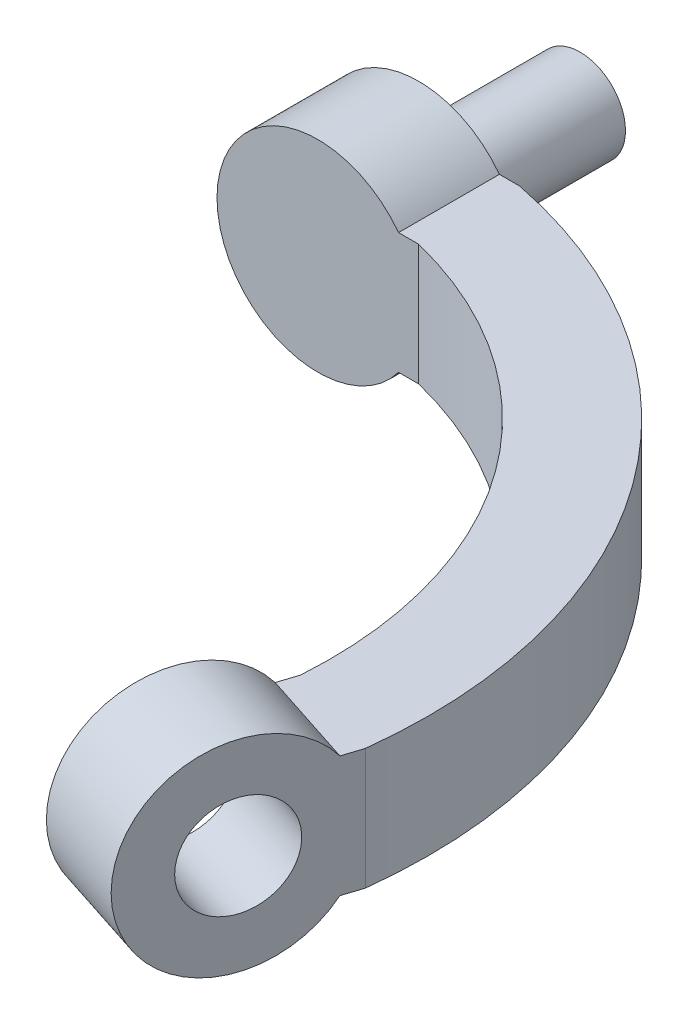
SolidWorks part; units mm, degrees
ref_plane "前视基准面" through (0, 0, 0) normal (0, 0, 1) x (1, 0, 0)
ref_plane "上视基准面" through (0, 0, 0) normal (0, 1, 0) x (1, 0, 0)
ref_plane "右视基准面" through (0, 0, 0) normal (1, 0, 0) x (0, 0, -1)
other "Configuration Table"
sketch "草图2" plane through (0, 0, 0) normal (0, 0, 1) x (1, 0, 0)
  circle A0 centre (0, 0) radius 5
  dimension "D1" = 10
extrude "凸台-拉伸3" add sketch "草图2" along normal blind 5
sketch "草图3" plane through (0, 0, 0) normal (0, 1, 0) x (1, 0, 0)
  line L0 (0, 0) -> (0, -25) construction
  line L1 (0, -25) -> (22.125, -32.1888) construction
  line L2 (20.5662, -26.4251) -> (25.3215, -27.9701)
  line L3 (0, 0) -> (5, 0)
  line L4 (0, 0) -> (0, -5)
  line L5 (0, -5) -> (5, -5)
  line L6 (5, 0) -> (5, -5)
  line L15 (25.3215, -27.9701) -> (23.7764, -32.7254)
  line L16 (23.7764, -32.7254) -> (19.0211, -31.1803)
  line L17 (19.0211, -31.1803) -> (20.5662, -26.4251)
  arc A0 (5, -5) -> (20.5662, -26.4251) centre (0, -25) cw
  arc A1 (5, 0) -> (25.3215, -27.9701) centre (0, -25) cw
  dimension "D4" = 20
  dimension "D1" = 108
  dimension "D2" = 5
  dimension "D3" = 5
  dimension "D5" = 5
extrude "凸台-拉伸4" add sketch "草图3" along normal blind 3 and the other way blind 3 separate body contours A1 L6 A0 L2 region at (17.1436, 0, 12.5444)
revolve "旋转1" add sketch "草图3<3>" angle 360 about L1 region at (22.1713, 0, 29.5752)
sketch "草图3<3>" plane through (0, 0, 0) normal (0, 1, 0) x (1, 0, 0) same geometry as "草图3"
sketch "草图4" plane through (-5.8022, 0, 17.8574) normal (-0.309, 0, 0.9511) x (0.9511, 0, 0.309)
  line L4 (32.7254, 3) -> (27.7254, 3)
  line L5 (27.7254, 3) -> (27.7254, -3)
  line L6 (27.7254, -3) -> (32.7254, -3)
  line L7 (32.7254, -3) -> (32.7254, 3)
  line L8 (32.7254, 3) -> (27.7254, 3)
  line L9 (27.7254, 3) -> (27.7254, -3)
  line L10 (27.7254, -3) -> (32.7254, -3)
  line L11 (32.7254, -3) -> (32.7254, 3)
  dimension "D1" = 0
extrude "凸台-拉伸5" add sketch "草图4" along normal blind 3
sketch "草图5" plane through (5, 0, 0) normal (-1, 0, 0) x (0, 0, 1)
  line L4 (5, -3) -> (5, 3)
  line L5 (5, 3) -> (0, 3)
  line L6 (0, 3) -> (0, -3)
  line L7 (0, -3) -> (5, -3)
  line L8 (5, -3) -> (5, 3)
  line L9 (5, 3) -> (0, 3)
  line L10 (0, 3) -> (0, -3)
  line L11 (0, -3) -> (5, -3)
  dimension "D1" = 0
extrude "凸台-拉伸6" add sketch "草图5" along normal blind 3
sketch "草图6" plane through (26.3684, 0, 8.5676) normal (-0.9511, 0, -0.309) x (-0.309, 0, 0.9511)
  circle A0 centre (23.7764, 0) radius 2.5
  dimension "D1" = 5
extrude "切除-拉伸1" cut sketch "草图6" against normal blind 5
sketch "草图7" plane through (0, 0, 5) normal (0, 0, 1) x (1, 0, 0)
  circle A0 centre (0, 0) radius 2.25
  dimension "D1" = 4.5
extrude "凸台-拉伸7" add sketch "草图7" against normal blind 8 from surface starting at face at (2.25, 0, 0)
